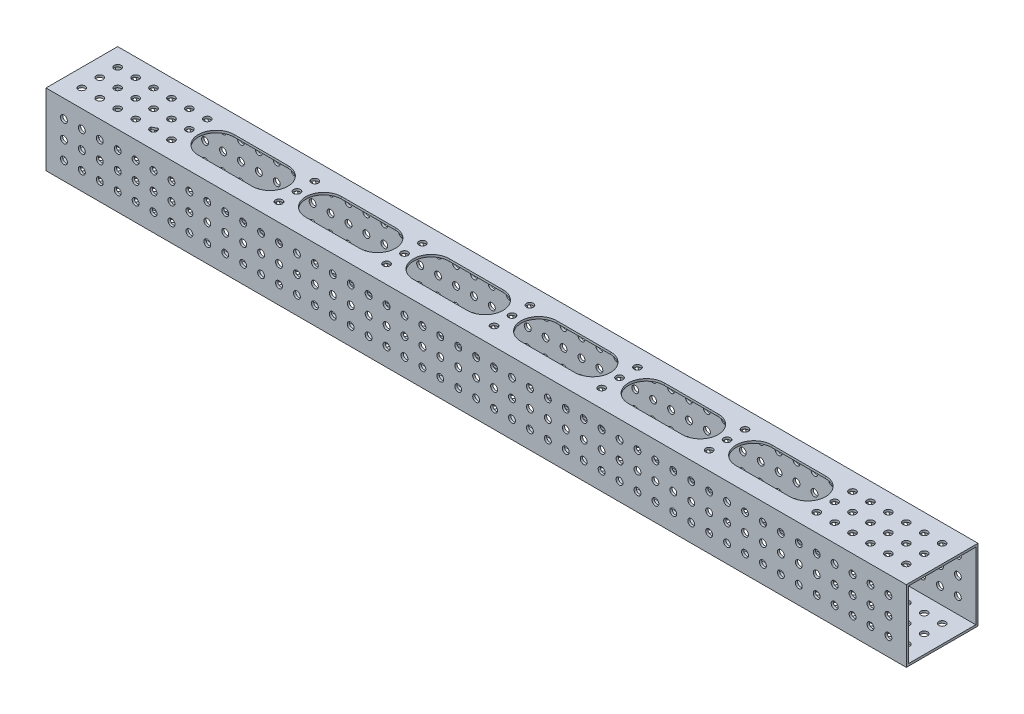
SolidWorks part; units mm, degrees
ref_plane "Front Plane" through (0, 0, 0) normal (0, 0, 1) x (1, 0, 0)
ref_plane "Top Plane" through (0, 0, 0) normal (0, 1, 0) x (1, 0, 0)
ref_plane "Right Plane" through (0, 0, 0) normal (1, 0, 0) x (0, 0, -1)
sketch "Sketch1" plane through (0, 0, 0) normal (1, 0, 0) x (0, 0, -1)
  line L1 (-25.4, -25.4) -> (25.4, -25.4)
  line L2 (-25.4, -25.4) -> (-25.4, 25.4)
  line L3 (-25.4, 25.4) -> (25.4, 25.4)
  line L4 (25.4, -25.4) -> (25.4, 25.4)
  line L5 (-25.4, -25.4) -> (25.4, 25.4) construction
  line L6 (-25.4, 25.4) -> (25.4, -25.4) construction
  line L7 (-23.8125, -23.8125) -> (23.8125, -23.8125)
  line L8 (-23.8125, -23.8125) -> (-23.8125, 23.8125)
  line L9 (-23.8125, 23.8125) -> (23.8125, 23.8125)
  line L10 (23.8125, -23.8125) -> (23.8125, 23.8125)
  line L11 (-23.8125, -23.8125) -> (23.8125, 23.8125) construction
  line L12 (-23.8125, 23.8125) -> (23.8125, -23.8125) construction
  point P0 (0, 0)
  point P7 (0, 0)
  dimension "D1" = 50.8
  dimension "D2" = 50.8
  dimension "D3" = 47.625
extrude "Boss-Extrude1" add sketch "Sketch1" along normal blind 609.6
sketch "Sketch2" plane through (0, 0, 25.4) normal (0, 0, 1) x (1, 0, 0)
  line L0 (-1000, 0) -> (49000, 0) construction
  line L2 (-994.1549, 12.7) -> (49005.8451, 12.7) construction
  line L3 (-984.8446, -12.7) -> (49015.1554, -12.7) construction
  line L4 (609.6, 25.4) -> (0, 25.4) construction
  line L5 (609.6, -25.4) -> (0, -25.4) construction
  line L6 (0, 25.4) -> (0, -25.4) construction
  line L7 (12.7, 12.7) -> (12.7, 0) construction
  line L8 (12.7, 12.7) -> (25.4, 12.7) construction
  circle A24 centre (12.7, 12.7) radius 2.4384
  circle A25 centre (12.7, 0) radius 2.4384
  circle A26 centre (12.7, -12.7) radius 2.4384
  circle A27 centre (25.4, 12.7) radius 2.4384
  circle A28 centre (25.4, 0) radius 2.4384
  circle A29 centre (25.4, -12.7) radius 2.4384
  circle A30 centre (38.1, 12.7) radius 2.4384
  circle A31 centre (38.1, 0) radius 2.4384
  circle A32 centre (38.1, -12.7) radius 2.4384
  circle A33 centre (50.8, 12.7) radius 2.4384
  circle A34 centre (50.8, 0) radius 2.4384
  circle A35 centre (50.8, -12.7) radius 2.4384
  circle A36 centre (63.5, 12.7) radius 2.4384
  circle A37 centre (63.5, 0) radius 2.4384
  circle A38 centre (63.5, -12.7) radius 2.4384
  circle A39 centre (76.2, 12.7) radius 2.4384
  circle A40 centre (76.2, 0) radius 2.4384
  circle A41 centre (76.2, -12.7) radius 2.4384
  circle A42 centre (88.9, 12.7) radius 2.4384
  circle A43 centre (88.9, 0) radius 2.4384
  circle A44 centre (88.9, -12.7) radius 2.4384
  circle A45 centre (101.6, 12.7) radius 2.4384
  circle A46 centre (101.6, 0) radius 2.4384
  circle A47 centre (101.6, -12.7) radius 2.4384
  circle A48 centre (114.3, 12.7) radius 2.4384
  circle A49 centre (114.3, 0) radius 2.4384
  circle A50 centre (114.3, -12.7) radius 2.4384
  circle A51 centre (127, 12.7) radius 2.4384
  circle A52 centre (127, 0) radius 2.4384
  circle A53 centre (127, -12.7) radius 2.4384
  circle A54 centre (139.7, 12.7) radius 2.4384
  circle A55 centre (139.7, 0) radius 2.4384
  circle A56 centre (139.7, -12.7) radius 2.4384
  circle A57 centre (152.4, 12.7) radius 2.4384
  circle A58 centre (152.4, 0) radius 2.4384
  circle A59 centre (152.4, -12.7) radius 2.4384
  circle A60 centre (165.1, 12.7) radius 2.4384
  circle A61 centre (165.1, 0) radius 2.4384
  circle A62 centre (165.1, -12.7) radius 2.4384
  circle A63 centre (177.8, 12.7) radius 2.4384
  circle A64 centre (177.8, 0) radius 2.4384
  circle A65 centre (177.8, -12.7) radius 2.4384
  circle A66 centre (190.5, 12.7) radius 2.4384
  circle A67 centre (190.5, 0) radius 2.4384
  circle A68 centre (190.5, -12.7) radius 2.4384
  circle A69 centre (203.2, 12.7) radius 2.4384
  circle A70 centre (203.2, 0) radius 2.4384
  circle A71 centre (203.2, -12.7) radius 2.4384
  circle A72 centre (215.9, 12.7) radius 2.4384
  circle A73 centre (215.9, 0) radius 2.4384
  circle A74 centre (215.9, -12.7) radius 2.4384
  circle A75 centre (228.6, 12.7) radius 2.4384
  circle A76 centre (228.6, 0) radius 2.4384
  circle A77 centre (228.6, -12.7) radius 2.4384
  circle A78 centre (241.3, 12.7) radius 2.4384
  circle A79 centre (241.3, 0) radius 2.4384
  circle A80 centre (241.3, -12.7) radius 2.4384
  circle A81 centre (254, 12.7) radius 2.4384
  circle A82 centre (254, 0) radius 2.4384
  circle A83 centre (254, -12.7) radius 2.4384
  circle A84 centre (266.7, 12.7) radius 2.4384
  circle A85 centre (266.7, 0) radius 2.4384
  circle A86 centre (266.7, -12.7) radius 2.4384
  circle A87 centre (279.4, 12.7) radius 2.4384
  circle A88 centre (279.4, 0) radius 2.4384
  circle A89 centre (279.4, -12.7) radius 2.4384
  circle A90 centre (292.1, 12.7) radius 2.4384
  circle A91 centre (292.1, 0) radius 2.4384
  circle A92 centre (292.1, -12.7) radius 2.4384
  circle A93 centre (304.8, 12.7) radius 2.4384
  circle A94 centre (304.8, 0) radius 2.4384
  circle A95 centre (304.8, -12.7) radius 2.4384
  circle A96 centre (317.5, 12.7) radius 2.4384
  circle A97 centre (317.5, 0) radius 2.4384
  circle A98 centre (317.5, -12.7) radius 2.4384
  circle A99 centre (330.2, 12.7) radius 2.4384
  circle A100 centre (330.2, 0) radius 2.4384
  circle A101 centre (330.2, -12.7) radius 2.4384
  circle A102 centre (342.9, 12.7) radius 2.4384
  circle A103 centre (342.9, 0) radius 2.4384
  circle A104 centre (342.9, -12.7) radius 2.4384
  circle A105 centre (355.6, 12.7) radius 2.4384
  circle A106 centre (355.6, 0) radius 2.4384
  circle A107 centre (355.6, -12.7) radius 2.4384
  circle A108 centre (368.3, 12.7) radius 2.4384
  circle A109 centre (368.3, 0) radius 2.4384
  circle A110 centre (368.3, -12.7) radius 2.4384
  circle A111 centre (381, 12.7) radius 2.4384
  circle A112 centre (381, 0) radius 2.4384
  circle A113 centre (381, -12.7) radius 2.4384
  circle A114 centre (393.7, 12.7) radius 2.4384
  circle A115 centre (393.7, 0) radius 2.4384
  circle A116 centre (393.7, -12.7) radius 2.4384
  circle A117 centre (406.4, 12.7) radius 2.4384
  circle A118 centre (406.4, 0) radius 2.4384
  circle A119 centre (406.4, -12.7) radius 2.4384
  circle A120 centre (419.1, 12.7) radius 2.4384
  circle A121 centre (419.1, 0) radius 2.4384
  circle A122 centre (419.1, -12.7) radius 2.4384
  circle A123 centre (431.8, 12.7) radius 2.4384
  circle A124 centre (431.8, 0) radius 2.4384
  circle A125 centre (431.8, -12.7) radius 2.4384
  circle A126 centre (444.5, 12.7) radius 2.4384
  circle A127 centre (444.5, 0) radius 2.4384
  circle A128 centre (444.5, -12.7) radius 2.4384
  circle A129 centre (457.2, 12.7) radius 2.4384
  circle A130 centre (457.2, 0) radius 2.4384
  circle A131 centre (457.2, -12.7) radius 2.4384
  circle A132 centre (469.9, 12.7) radius 2.4384
  circle A133 centre (469.9, 0) radius 2.4384
  circle A134 centre (469.9, -12.7) radius 2.4384
  circle A135 centre (482.6, 12.7) radius 2.4384
  circle A136 centre (482.6, 0) radius 2.4384
  circle A137 centre (482.6, -12.7) radius 2.4384
  circle A138 centre (495.3, 12.7) radius 2.4384
  circle A139 centre (495.3, 0) radius 2.4384
  circle A140 centre (495.3, -12.7) radius 2.4384
  circle A141 centre (508, 12.7) radius 2.4384
  circle A142 centre (508, 0) radius 2.4384
  circle A143 centre (508, -12.7) radius 2.4384
  circle A144 centre (520.7, 12.7) radius 2.4384
  circle A145 centre (520.7, 0) radius 2.4384
  circle A146 centre (520.7, -12.7) radius 2.4384
  circle A147 centre (533.4, 12.7) radius 2.4384
  circle A148 centre (533.4, 0) radius 2.4384
  circle A149 centre (533.4, -12.7) radius 2.4384
  circle A150 centre (546.1, 12.7) radius 2.4384
  circle A151 centre (546.1, 0) radius 2.4384
  circle A152 centre (546.1, -12.7) radius 2.4384
  circle A153 centre (558.8, 12.7) radius 2.4384
  circle A154 centre (558.8, 0) radius 2.4384
  circle A155 centre (558.8, -12.7) radius 2.4384
  circle A156 centre (571.5, 12.7) radius 2.4384
  circle A157 centre (571.5, 0) radius 2.4384
  circle A158 centre (571.5, -12.7) radius 2.4384
  circle A159 centre (584.2, 12.7) radius 2.4384
  circle A160 centre (584.2, 0) radius 2.4384
  circle A161 centre (584.2, -12.7) radius 2.4384
  circle A162 centre (596.9, 12.7) radius 2.4384
  circle A163 centre (596.9, 0) radius 2.4384
  circle A164 centre (596.9, -12.7) radius 2.4384
  dimension "D1" = 12.7
  dimension "D3" = 4.8768
  dimension "D2" = 12.7
  dimension "D4" = 12.7
  dimension "D6" = 12.7
  dimension "D8" = 12.7
  dimension "D5" = 3
  dimension "D7" = 47
extrude "Cut-Extrude2" cut sketch "Sketch2" against normal blind 609.6
sketch "Sketch3" plane through (0, -25.4, 0) normal (0, -1, 0) x (1, 0, 0)
  line L0 (0, 0) -> (6.35, 0)
  line L1 (76.2, 12.7) -> (63.5, 12.7) construction
  line L2 (0, 25.4) -> (0, -25.4) construction
  line L3 (19.05, 12.7) -> (57.15, 12.7)
  line L4 (19.05, -12.7) -> (57.15, -12.7)
  line L5 (609.6, 25.4) -> (0, 25.4) construction
  line L6 (95.25, 12.7) -> (133.35, 12.7)
  line L7 (95.25, -12.7) -> (133.35, -12.7)
  line L8 (171.45, 12.7) -> (209.55, 12.7)
  line L9 (171.45, -12.7) -> (209.55, -12.7)
  line L10 (247.65, 12.7) -> (285.75, 12.7)
  line L11 (247.65, -12.7) -> (285.75, -12.7)
  line L12 (323.85, 12.7) -> (361.95, 12.7)
  line L13 (323.85, -12.7) -> (361.95, -12.7)
  line L14 (400.05, 12.7) -> (438.15, 12.7)
  line L15 (400.05, -12.7) -> (438.15, -12.7)
  line L16 (476.25, 12.7) -> (514.35, 12.7)
  line L17 (476.25, -12.7) -> (514.35, -12.7)
  line L18 (552.45, 12.7) -> (590.55, 12.7)
  line L19 (552.45, -12.7) -> (590.55, -12.7)
  line L20 (535.8384, 0) -> (539.75, 0)
  line L21 (527.05, 0) -> (530.9616, 0)
  line L22 (383.4384, 0) -> (387.35, 0)
  line L23 (374.65, 0) -> (378.5616, 0)
  line L24 (459.6384, 0) -> (463.55, 0)
  line L25 (146.05, 0) -> (149.9616, 0)
  line L26 (222.25, 0) -> (226.1616, 0)
  line L27 (154.8384, 0) -> (158.75, 0)
  line L28 (307.2384, 0) -> (311.15, 0)
  line L29 (298.45, 0) -> (302.3616, 0)
  line L30 (231.0384, 0) -> (234.95, 0)
  line L31 (69.85, 0) -> (73.7616, 0)
  line L32 (78.6384, 0) -> (82.55, 0)
  line L33 (19.05, 12.7) -> (95.25, 12.7) construction
  arc A0 (19.05, 12.7) -> (19.05, -12.7) centre (19.05, 0) ccw
  arc A1 (57.15, -12.7) -> (57.15, 12.7) centre (57.15, 0) ccw
  circle A2 centre (76.2, 12.7) radius 2.4384
  circle A3 centre (76.2, 0) radius 2.4384
  circle A4 centre (76.2, -12.7) radius 2.4384
  arc A5 (95.25, 12.7) -> (95.25, -12.7) centre (95.25, 0) ccw
  arc A6 (133.35, -12.7) -> (133.35, 12.7) centre (133.35, 0) ccw
  circle A7 centre (152.4, 12.7) radius 2.4384
  circle A8 centre (152.4, 0) radius 2.4384
  circle A9 centre (152.4, -12.7) radius 2.4384
  arc A10 (171.45, 12.7) -> (171.45, -12.7) centre (171.45, 0) ccw
  arc A11 (209.55, -12.7) -> (209.55, 12.7) centre (209.55, 0) ccw
  circle A12 centre (228.6, 12.7) radius 2.4384
  circle A13 centre (228.6, 0) radius 2.4384
  circle A14 centre (228.6, -12.7) radius 2.4384
  arc A15 (247.65, 12.7) -> (247.65, -12.7) centre (247.65, 0) ccw
  arc A16 (285.75, -12.7) -> (285.75, 12.7) centre (285.75, 0) ccw
  circle A17 centre (304.8, 12.7) radius 2.4384
  circle A18 centre (304.8, 0) radius 2.4384
  circle A19 centre (304.8, -12.7) radius 2.4384
  arc A20 (323.85, 12.7) -> (323.85, -12.7) centre (323.85, 0) ccw
  arc A21 (361.95, -12.7) -> (361.95, 12.7) centre (361.95, 0) ccw
  circle A22 centre (381, 12.7) radius 2.4384
  circle A23 centre (381, 0) radius 2.4384
  circle A24 centre (381, -12.7) radius 2.4384
  arc A25 (400.05, 12.7) -> (400.05, -12.7) centre (400.05, 0) ccw
  arc A26 (438.15, -12.7) -> (438.15, 12.7) centre (438.15, 0) ccw
  circle A27 centre (457.2, 12.7) radius 2.4384
  circle A28 centre (457.2, 0) radius 2.4384
  circle A29 centre (457.2, -12.7) radius 2.4384
  arc A30 (476.25, 12.7) -> (476.25, -12.7) centre (476.25, 0) ccw
  arc A31 (514.35, -12.7) -> (514.35, 12.7) centre (514.35, 0) ccw
  circle A32 centre (533.4, 12.7) radius 2.4384
  circle A33 centre (533.4, 0) radius 2.4384
  circle A34 centre (533.4, -12.7) radius 2.4384
  arc A35 (552.45, 12.7) -> (552.45, -12.7) centre (552.45, 0) ccw
  arc A36 (590.55, -12.7) -> (590.55, 12.7) centre (590.55, 0) ccw
  circle A40 centre (609.6, 12.7) radius 2.4384 [skipped]
  circle A41 centre (609.6, 0) radius 2.4384 [skipped]
  circle A42 centre (609.6, -12.7) radius 2.4384 [skipped]
  circle A43 centre (546.1, 12.7) radius 2.4384
  circle A44 centre (546.1, 0) radius 2.4384
  circle A45 centre (546.1, -12.7) radius 2.4384
  circle A46 centre (558.8, 12.7) radius 2.4384
  circle A47 centre (558.8, 0) radius 2.4384
  circle A48 centre (558.8, -12.7) radius 2.4384
  circle A49 centre (571.5, 12.7) radius 2.4384
  circle A50 centre (571.5, 0) radius 2.4384
  circle A51 centre (571.5, -12.7) radius 2.4384
  circle A52 centre (584.2, 12.7) radius 2.4384
  circle A53 centre (584.2, 0) radius 2.4384
  circle A54 centre (584.2, -12.7) radius 2.4384
  circle A55 centre (596.9, 12.7) radius 2.4384
  circle A56 centre (596.9, 0) radius 2.4384
  circle A57 centre (596.9, -12.7) radius 2.4384
  circle A58 centre (63.5, 12.7) radius 2.4384
  circle A59 centre (63.5, -12.7) radius 2.4384
  circle A60 centre (63.5, 0) radius 2.4384
  circle A61 centre (50.8, 12.7) radius 2.4384
  circle A62 centre (50.8, -12.7) radius 2.4384
  circle A63 centre (50.8, 0) radius 2.4384
  circle A64 centre (38.1, 12.7) radius 2.4384
  circle A65 centre (38.1, -12.7) radius 2.4384
  circle A66 centre (38.1, 0) radius 2.4384
  circle A67 centre (25.4, 12.7) radius 2.4384
  circle A68 centre (25.4, -12.7) radius 2.4384
  circle A69 centre (25.4, 0) radius 2.4384
  circle A70 centre (12.7, 12.7) radius 2.4384
  circle A71 centre (12.7, -12.7) radius 2.4384
  circle A72 centre (12.7, 0) radius 2.4384
  point P11 (0, 0)
  point P27 (0, 0)
  dimension "D1" = 25.4
  dimension "D2" = 19.05
  dimension "D3" = 25.4
  dimension "D4" = 38.1
  dimension "D5" = 4.8768
  dimension ".2" = 4.8768
  dimension "D6" = 4.8768
  dimension "D8" = 12.7
  dimension "D9" = 12.7
  dimension "D10" = 76.2
  dimension "D11" = 76.2
  dimension "D12" = 76.2
  dimension "D7" = 12.7
  dimension "D15" = 76.2
  dimension "D16" = 6
  dimension "D17" = 12.7
  dimension "D18" = 12.7
  dimension "D13" = 8
  dimension "D14" = 6
extrude "Cut-Extrude3" cut sketch "Sketch3" against normal blind 76.2 contours L7 A6 L6 A5 | L9 A11 L8 A10 | L11 A16 L10 A15 | L13 A21 L12 A20 | A4 | A8 | A9 | A7 | A18 | A23 | L15 A26 L14 A25 | A28 | L17 A31 L16 A30 | A63 | A66 | A69 | A1 A58 | A2 | A3 | A12 | A13 | A14 | A17 | A19 | A22 | A24 | A27 | A29 | A33 | A32 | A34 | A62 | A61 | A64 | A65 | A68 | A67 | A70 | A72 | A71 | A60 | A59 | A45 | A48 | A51 | A44 | A43 | A46 | A49 | A52 | A53 | A50 | A47 | A54 | A57 | A56 | A55 region at (419.1, -25.4, 0) region at (381, -25.4, 0) region at (342.9, -25.4, 0) region at (304.8, -25.4, 0) region at (266.7, -25.4, 0) region at (190.5, -25.4, 0) region at (152.4, -25.4, 0) region at (114.3, -25.4, 0) region at (63.6226, -25.4, 12.9453) region at (457.2, -25.4, 0) region at (495.3, -25.4, 0) region at (76.2, -25.4, -12.7) region at (152.4, -25.4, 12.7) region at (152.4, -25.4, -12.7) region at (50.8, -25.4, 0) region at (38.1, -25.4, 0) region at (25.4, -25.4, 0)
